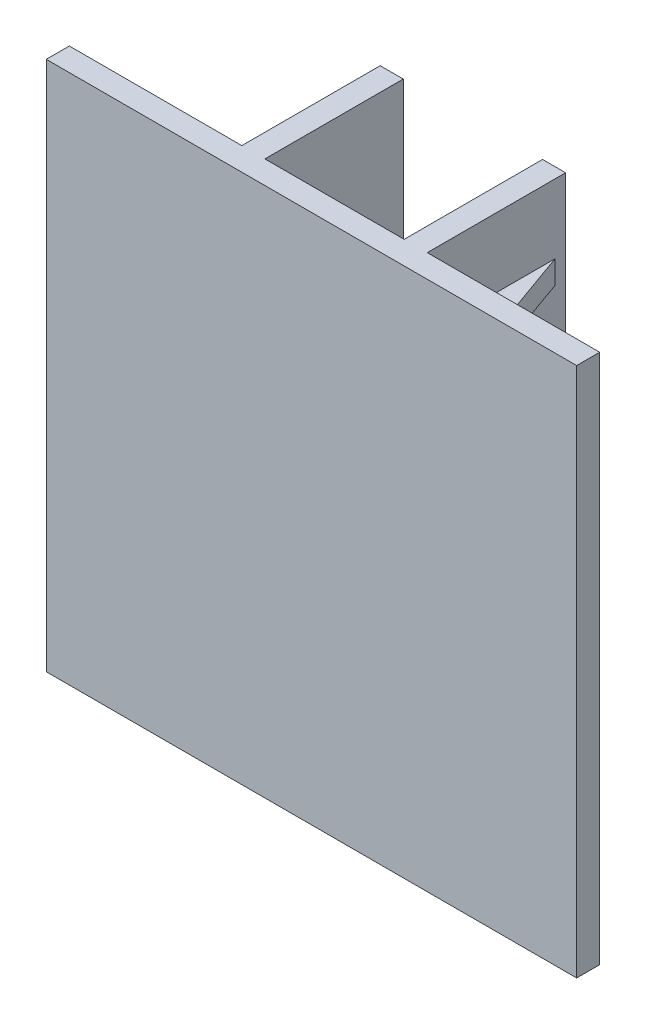
SolidWorks part; units mm, degrees
ref_plane "정면" through (0, 0, 0) normal (0, 0, 1) x (1, 0, 0)
ref_plane "윗면" through (0, 0, 0) normal (0, 1, 0) x (1, 0, 0)
ref_plane "우측면" through (0, 0, 0) normal (1, 0, 0) x (0, 0, -1)
sketch "스케치1" plane through (0, 0, 0) normal (0, 0, 1) x (1, 0, 0)
  line L0 (-132.2193, 0) -> (132.2193, 0) construction
  line L1 (0, 91.7848) -> (0, -91.7848) construction
  line L2 (-57.5, 57.5) -> (-57.5, -57.5)
  line L3 (-57.5, -57.5) -> (57.5, -57.5)
  line L4 (57.5, -57.5) -> (57.5, 57.5)
  line L5 (57.5, 57.5) -> (-57.5, 57.5)
  line L6 (15.1, 57.5) -> (15.1, -57.5)
  line L7 (20.1, 57.5) -> (20.1, -57.5)
  line L8 (-20.1, 57.5) -> (-20.1, -57.5)
  line L9 (-15.1, 57.5) -> (-15.1, -57.5)
  line L10 (0, 0) -> (0, 40) construction
  point P5 (0, 0)
  point P6 (-57.5, 0)
  point P7 (0, 0)
  point P11 (0, -57.5)
  point P18 (0, 0)
  dimension "D1" = 115
  dimension "D2" = 115
  dimension "D4" = 15.1
  dimension "D5" = 5
  dimension "D6" = 40
  dimension "D3" = 2
sketch "스케치2" plane through (0, 0, 0) normal (0, 1, 0) x (1, 0, 0)
  line L0 (0, 0) -> (-31.9862, 0) construction
  line L1 (-132.2193, 0) -> (132.2193, 0) construction
extrude "보스-돌출1" add sketch "스케치1" against normal blind 30 contours L9 L5 L8 L3 | L7 L5 L6 L3 region at (-17.6, 0, 0) region at (17.6, 0, 0)
extrude "보스-돌출2" add sketch "스케치1<3>" along normal blind 5 contours L8 L5 L2 L3 | L5 L9 L3 L6 | L9 L5 L8 L3 | L7 L5 L6 L3 | L5 L7 L3 L4 region at (-38.8, 0, 0) region at (-17.6, 0, 0) region at (0, 0, 0) region at (17.6, 0, 0) region at (38.8, 0, 0)
sketch "스케치1<3>" plane through (0, 0, 0) normal (0, 0, 1) x (1, 0, 0) same geometry as "스케치1"
sketch "스케치3" plane through (0, 0, 0) normal (1, 0, 0) x (0, 0, -1)
  line L0 (0, 0) -> (0, 20) construction
  line L1 (0, 20) -> (30, 20) construction
  line L2 (30, 20) -> (15, 20)
  line L3 (15, 24) -> (30, 24)
  line L4 (15, 16) -> (30, 16)
  line L5 (30, 16) -> (30, 24)
  line L6 (0, 0) -> (30, 0) construction
  line L7 (30, -16) -> (30, -24)
  line L8 (15, -16) -> (30, -16)
  line L9 (15, -24) -> (30, -24)
  arc A0 (15, 24) -> (15, 16) centre (15, 20) ccw
  arc A1 (15, -24) -> (15, -16) centre (15, -20) cw
  dimension "D4" = 4
  dimension "D1" = 16
  dimension "D2" = 15
  dimension "D3" = 30
  dimension "D5" = 16
extrude "컷-돌출1" cut sketch "스케치3" along direction (-1, 0, 0) on the side against the normal mid plane 45 contours L8 L7 L9 A1 | L3 L5 L4 A0
sketch "스케치4" plane through (0, 0, 0) normal (0, 1, 0) x (1, 0, 0)
  line L0 (0, 0) -> (0, 28) construction
  line L1 (0, 28) -> (20, 28) construction
  line L3 (0, 0) -> (60, 0) construction
  line L5 (20, 28) -> (48, 0)
  dimension "D1" = 28
  dimension "D2" = 20
  dimension "D3" = 60
  dimension "D4" = 45
rib "보강대1" sketch "스케치4" sketch "스케치4" thickness 5 extrusion direction parallel to sketch draft on no parameters "D1"=5
sketch "스케치6" plane through (0, 0, 0) normal (0, 0, 1) x (1, 0, 0)
  line L0 (0, 0) -> (0, 40)
  dimension "D1" = 40
sketch3d "3D스케치1"
  line L0 (0, 40, 0) -> (0, 40, -28)
  line L1 (0, 40, -28) -> (20, 40, -28)
  line L2 (0, 40, 0) -> (20, 40, 0) construction
  line L3 (20, 40, 0) -> (30, 40, 0) construction
  line L4 (20, 40, -28) -> (30, 40, 0)
  line L5 (0, 0, 0) -> (0, 0, -24.6493) construction
  dimension "D1" = 28
  dimension "D2" = 20
  dimension "D3" = 20
  dimension "D4" = 10
ref_plane "평면1" through (0, 40, 0) normal (0, 1, 0) x (1, 0, 0)
sketch "스케치7" plane through (0, 40, 0) normal (0, 1, 0) x (1, 0, 0)
  line L0 (20, 28) -> (30, 0)
  line L1 (20, 28) -> (20, 0) construction
  line L2 (20, 0) -> (30, 0) construction
rib "보강대2" sketch "스케치7" sketch "스케치7" thickness 5 extrusion direction parallel to sketch draft on no parameters "D1"=5
ref_plane "평면2" through (0, 0, 0) normal (-1, 0, 0) x (0, 0, 1)
mirror "대칭 복사1" about plane through (0, 0, 0) normal (-1, 0, 0) of "보강대1"
ref_plane "평면3" through (0, 0, 0) normal (0, -1, 0) x (-1, 0, 0)
mirror "대칭 복사2" about plane through (0, 0, 0) normal (-1, 0, 0) of "보강대2"
mirror "대칭 복사3" about plane through (0, 0, 0) normal (0, -1, 0) of "대칭 복사2"
